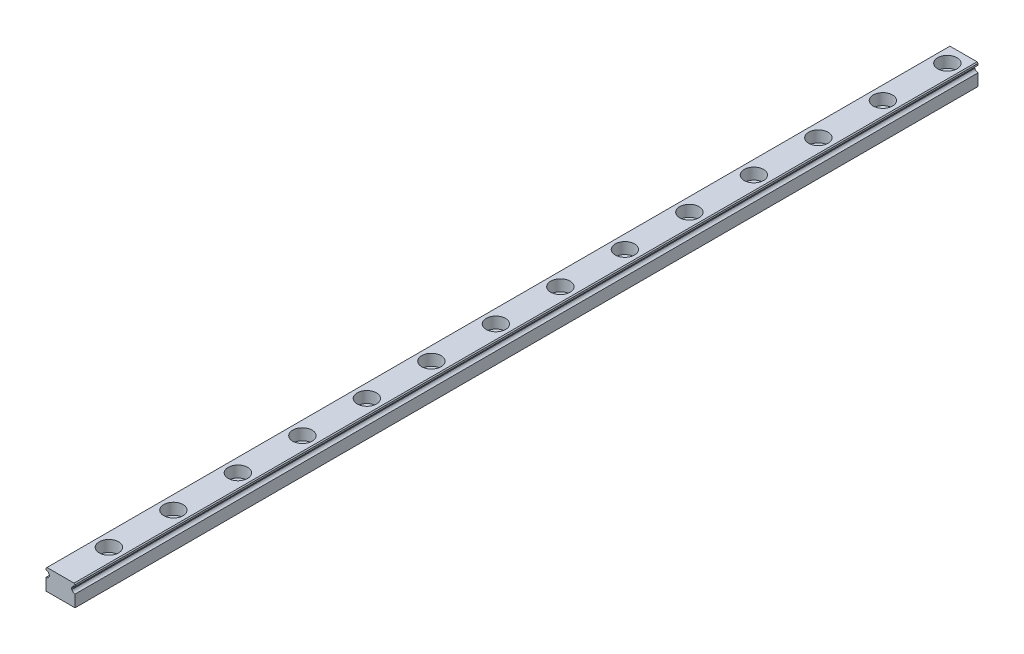
SolidWorks part; units mm, degrees
ref_plane "Спереди" through (0, 0, 0) normal (0, 0, 1) x (1, 0, 0)
ref_plane "Сверху" through (0, 0, 0) normal (0, 1, 0) x (1, 0, 0)
ref_plane "Справа" through (0, 0, 0) normal (1, 0, 0) x (0, 0, -1)
sketch "Sketch1" plane through (0, 0, 0) normal (0, 0, 1) x (1, 0, 0)
  line L0 (0, 0) -> (0, 5.7299) construction
  line L1 (-4.5, -3.25) -> (4.5, -3.25)
  line L2 (-4.5, -3.25) -> (-4.5, 0.45)
  line L3 (-4.5, 3.25) -> (4.5, 3.25)
  line L4 (4.5, -3.25) -> (4.5, 0.45)
  line L5 (-4.5, -3.25) -> (4.5, 3.25) construction
  line L6 (-4.5, 3.25) -> (4.5, -3.25) construction
  line L7 (-4.5, 2.45) -> (-4.5, 3.25)
  line L8 (-3.5318, 1.2) -> (-3.4, 1.2)
  line L9 (3.5318, 1.2) -> (3.4, 1.2)
  line L10 (-3.5318, 1.7) -> (-3.4, 1.7)
  line L11 (-3.4, 1.2) -> (-3.4, 1.7)
  line L12 (3.4, 1.2) -> (3.4, 1.7)
  line L13 (3.5318, 1.7) -> (3.4, 1.7)
  line L14 (4.5, 2.45) -> (4.5, 3.25)
  line L15 (-3.4, 1.45) -> (-4.5, 1.45) construction
  arc A0 (-3.5318, 1.7) -> (-4.5, 2.45) centre (-4.5, 1.45) ccw
  arc A1 (-4.5, 0.45) -> (-3.5318, 1.2) centre (-4.5, 1.45) ccw
  arc A2 (4.5, 0.45) -> (3.5318, 1.2) centre (4.5, 1.45) cw
  arc A3 (3.5318, 1.7) -> (4.5, 2.45) centre (4.5, 1.45) cw
  point P0 (0, 0)
  dimension "D3" = 1
  dimension "D1" = 9
  dimension "D2" = 6.5
  dimension "D4" = 2.05
  dimension "D5" = 6.8
  dimension "D6" = 0.5
extrude "Extrude1" add sketch "Sketch1" along normal blind 280
sketch "Sketch2" plane through (0, 3.25, 0) normal (0, 1, 0) x (1, 0, 0)
  line L0 (4.5, 0) -> (-4.5, 0) construction
  circle A0 centre (0, -5) radius 1.75
  circle A1 centre (0, -5) radius 3
  dimension "D1" = 3.5
  dimension "D2" = 6
  dimension "D3" = 5
extrude "Extrude2" cut sketch "Sketch2" against normal blind 3.5 contours A1
extrude "Extrude3" cut sketch "Sketch" against normal through all contours A0
sketch "Sketch" plane through (0, 3.25, 0) normal (0, 1, 0) x (1, 0, 0) same geometry as "Sketch2"
pattern_linear "LPattern1" count 40 spacing 20 along (0, 0, 1) of "Extrude2", "Extrude3"
chamfer "Chamfer1" distance 0.3 angle 45 2 edges at (4.5, 3.25, 140) (-4.5, 3.25, 140)
